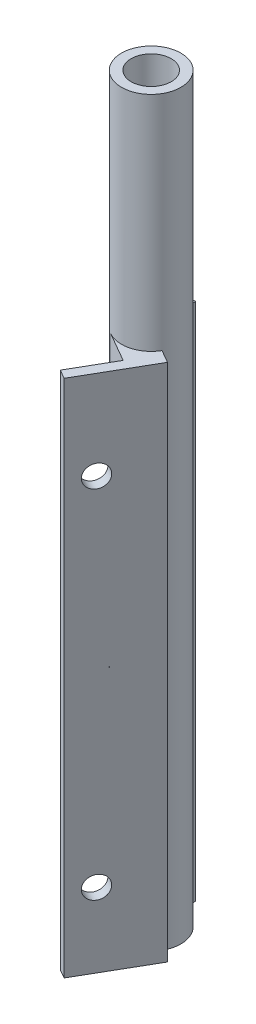
SolidWorks part; units mm, degrees
ref_plane "Front Plane" through (0, 0, 0) normal (0, 0, 1) x (1, 0, 0)
ref_plane "Top Plane" through (0, 0, 0) normal (0, 1, 0) x (1, 0, 0)
ref_plane "Right Plane" through (0, 0, 0) normal (1, 0, 0) x (0, 0, -1)
sketch "Sketch1" plane through (0, 0, 0) normal (0, 1, 0) x (1, 0, 0)
  circle A0 centre (0, 0) radius 5.08
  dimension "D1" = 10.16
extrude "Boss-Extrude1" add sketch "Sketch1" along normal blind 127
sketch "Sketch2" plane through (0, 0, 0) normal (0, -1, 0) x (1, 0, 0)
  circle A0 centre (0, 0) radius 3.429
  dimension "D1" = 6.858
extrude "Cut-Extrude1" cut sketch "Sketch2" against normal through all
sketch "Sketch3" plane through (0, 0, 0) normal (0, -1, 0) x (1, 0, 0)
  line L0 (0, 0) -> (0, -5.08) construction
  line L1 (0, -5.08) -> (-5.08, -5.08) construction
  line L2 (0, 0) -> (-2.54, 4.3994) construction
  line L3 (0, 0) -> (-5.08, 0) construction
  line L4 (-2.54, 4.3994) -> (1.8594, 6.9394) construction
  line L5 (8.7988, -5.08) -> (-1.4426, 12.6586) construction
  line L7 (0, -5.08) -> (-11.684, -5.08) construction
  line L8 (-1.4426, 12.6586) -> (-5.842, 10.1186)
  line L9 (-11.684, -5.08) -> (-11.684, 0)
  line L10 (-5.842, 10.1186) -> (-2.54, 4.3994)
  line L11 (-11.684, 0) -> (-5.08, 0)
  line L13 (-11.684, -5.08) -> (-11.684, -10.16)
  line L14 (-11.684, -10.16) -> (0, -10.16)
  line L15 (0, -10.16) -> (0, -5.08)
  line L17 (4.3994, 2.54) -> (8.7988, 5.08)
  line L18 (8.7988, 5.08) -> (2.9568, 15.1986)
  line L19 (2.9568, 15.1986) -> (-1.4426, 12.6586)
  arc A0 (-5.08, 0) -> (-2.54, 4.3994) centre (-0.7771, 0.4486) ccw
  circle A1 centre (0, 0) radius 3.429 construction
  circle A2 centre (0, 0) radius 5.08 construction
  arc A3 (4.3994, 2.54) -> (0, -5.08) centre (0, 0) cw
  point P9 (0, -5.08)
  dimension "D1" = 60
  dimension "D2" = 6.604
  dimension "D3" = 6.604
  dimension "D4" = 5.08
  dimension "D5" = 5.08
extrude "Boss-Extrude2" add sketch "Sketch3" against normal blind 88.9
sketch "Sketch4" plane through (0, 0, 0) normal (0, 0, 1) x (1, 0, 0)
  line L1 (-5.08, 88.9) -> (-5.08, 0) construction
  line L2 (-5.08, 88.9) -> (-11.684, 88.9) construction
  circle A0 centre (-8.89, 81.28) radius 1.905
  circle A1 centre (-8.89, 20.32) radius 1.905
  dimension "D3" = 3.81
  dimension "D1" = 7.62
  dimension "D2" = 68.58
  dimension "D4" = 3.81
extrude "Hole Cuts 1" cut sketch "Sketch4" against normal up to next
sketch "Sketch7" plane through (0, 0, 0) normal (0.866, 0, 0.5) x (0.5, 0, -0.866)
  line L1 (-5.08, 88.9) -> (-5.08, 0) construction
  line L3 (-2.54, 88.9) -> (-5.842, 88.9) construction
  line L5 (0, 88.9) -> (-11.684, 88.9) construction
  circle A0 centre (-8.89, 73.66) radius 1.905
  circle A1 centre (-8.89, 12.7) radius 1.905
  dimension "D2" = 3.81
  dimension "D1" = 3.81
  dimension "D3" = 15.24
  dimension "D4" = 76.2
extrude "Hole Cuts 2" cut sketch "Sketch7" along normal up to next
sketch "Sketch8" plane through (0, 0, 0) normal (0, -1, 0) x (1, 0, 0)
  line L0 (-5.842, 10.1186) -> (-1.8825, 12.4046)
  line L1 (2.9568, 15.1986) -> (-5.842, 10.1186) construction
  line L2 (-11.684, 0) -> (-11.684, -4.572)
  line L3 (-11.684, 0) -> (-11.684, -10.16) construction
  line L4 (-5.842, 10.1186) -> (-2.54, 4.3994)
  line L5 (-11.684, 0) -> (-5.08, 0)
  line L6 (-1.8825, 12.4046) -> (1.4195, 6.6854)
  line L7 (1.4195, 6.6854) -> (-2.54, 4.3994)
  line L8 (-11.684, -4.572) -> (-5.08, -4.572)
  line L9 (-5.08, -4.572) -> (-5.08, 0)
  dimension "D1" = 4.572
extrude "Cut-Extrude7" cut sketch "Sketch8" against normal up to next
sketch "Sketch9" plane through (0, 0, -10.16) normal (0, 0, -1) x (-1, 0, 0)
  line L1 (11.684, 88.9) -> (0, 88.9)
  line L2 (11.684, 88.9) -> (11.684, 0)
  line L3 (11.684, 0) -> (0, 0)
  line L4 (0, 88.9) -> (0, 0)
extrude "Cut-Extrude8" cut sketch "Sketch9" against normal blind 2.54
sketch "Sketch10" plane through (8.7988, 0, 5.08) normal (0.866, 0, 0.5) x (0.5, 0, -0.866)
  line L1 (-11.684, 0) -> (0, 0)
  line L2 (-11.684, 0) -> (-11.684, 88.9)
  line L3 (-11.684, 88.9) -> (0, 88.9)
  line L4 (0, 0) -> (0, 88.9)
extrude "Cut-Extrude9" cut sketch "Sketch10" against normal blind 2.54
sketch "Sketch11" plane through (0, 0, -4.572) normal (0, 0, 1) x (1, 0, 0)
  line L1 (-11.684, 88.9) -> (-5.08, 88.9)
  line L2 (-11.684, 88.9) -> (-11.684, 0)
  line L3 (-11.684, 0) -> (-5.08, 0)
  line L4 (-5.08, 88.9) -> (-5.08, 0)
extrude "Cut-Extrude10" cut sketch "Sketch11" against normal blind 1.27
sketch "Sketch13" plane through (3.9595, 0, 2.286) normal (-0.866, 0, -0.5) x (-0.5, 0, 0.866)
  line L1 (5.08, 0) -> (11.684, 0)
  line L2 (5.08, 0) -> (5.08, 88.9)
  line L3 (5.08, 88.9) -> (11.684, 88.9)
  line L4 (11.684, 0) -> (11.684, 88.9)
extrude "Cut-Extrude11" cut sketch "Sketch13" against normal blind 1.27
sketch "Sketch14" plane through (-5.842, 0, 10.1186) normal (-0.5, 0, 0.866) x (0.866, 0, 0.5)
  line L1 (7.62, 0) -> (5.842, 0)
  line L2 (7.62, 0) -> (7.62, 88.9)
  line L3 (7.62, 88.9) -> (5.842, 88.9)
  line L4 (5.842, 0) -> (5.842, 88.9)
extrude "Boss-Extrude3" add sketch "Sketch14" along normal blind 1.27
sketch "Sketch15" plane through (-11.684, 0, 0) normal (-1, 0, 0) x (0, 0, 1)
  line L1 (-5.842, 0) -> (-7.62, 0)
  line L2 (-5.842, 0) -> (-5.842, 88.9)
  line L3 (-5.842, 88.9) -> (-7.62, 88.9)
  line L4 (-7.62, 0) -> (-7.62, 88.9)
extrude "Boss-Extrude4" add sketch "Sketch15" along normal blind 1.27
